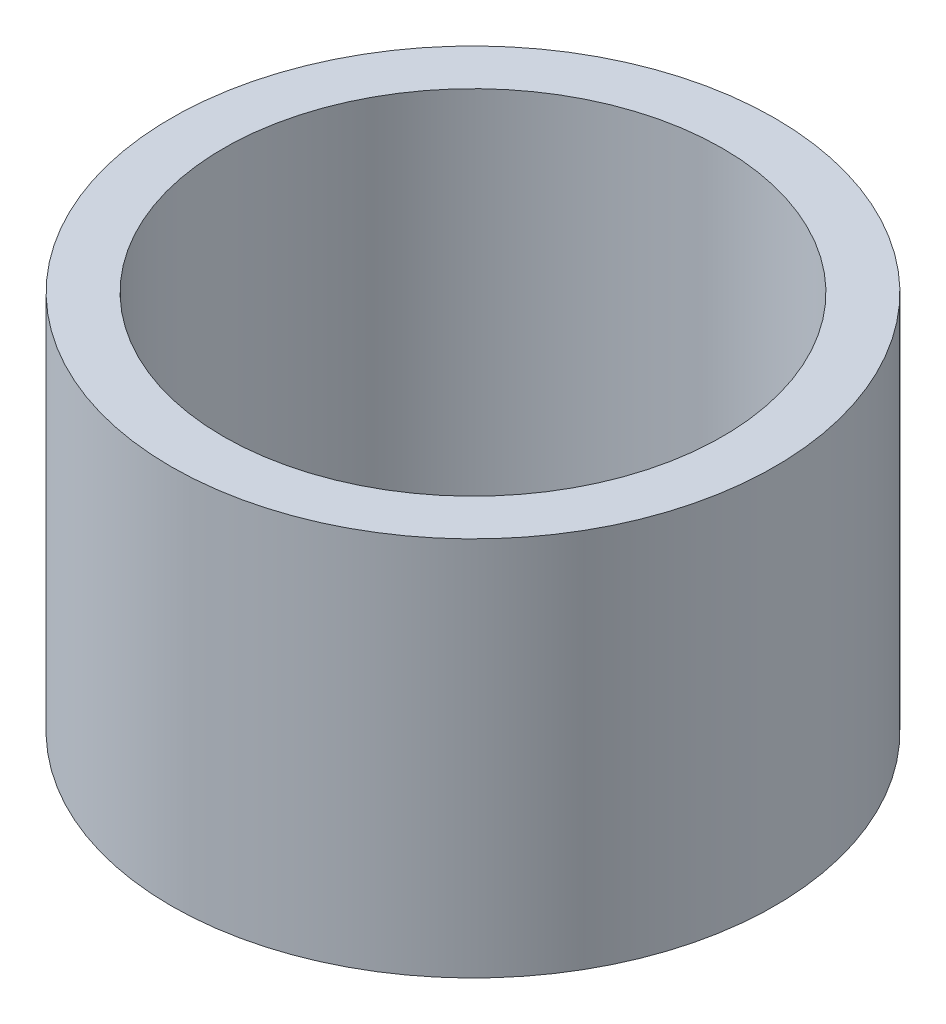
SolidWorks part; units mm, degrees
material "PETG"
ref_plane "Спереди" through (0, 0, 0) normal (0, 0, 1) x (1, 0, 0)
ref_plane "Сверху" through (0, 0, 0) normal (0, 1, 0) x (1, 0, 0)
ref_plane "Справа" through (0, 0, 0) normal (1, 0, 0) x (0, 0, -1)
sketch "Эскиз1" plane through (0, 0, 0) normal (0, 1, 0) x (1, 0, 0)
  circle A0 centre (0, 0) radius 5.25
  circle A1 centre (0, 0) radius 6.35
  dimension "D1" = 12.7
  dimension "D2" = 10.5
extrude "Бобышка-Вытянуть1" add sketch "Эскиз1" along normal blind 8
